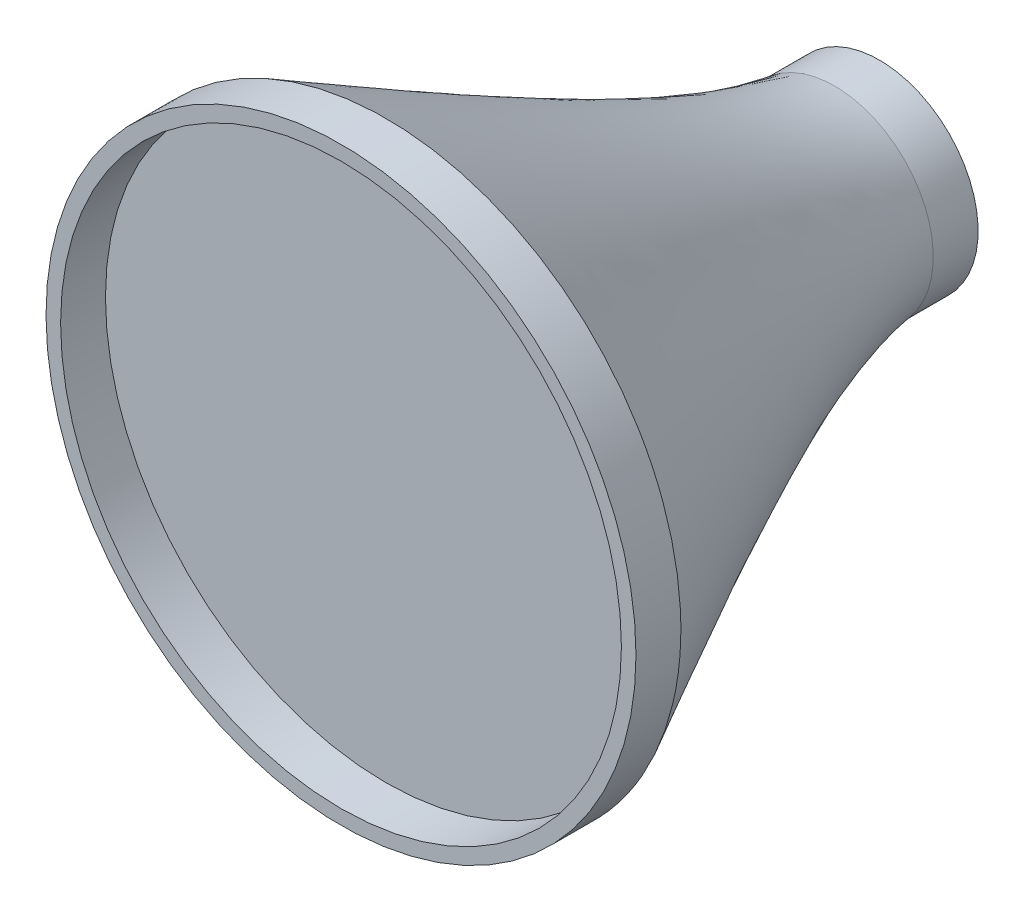
SolidWorks part; units mm, degrees
ref_plane "Front Plane" through (0, 0, 0) normal (0, 0, 1) x (1, 0, 0)
ref_plane "Top Plane" through (0, 0, 0) normal (0, 1, 0) x (1, 0, 0)
ref_plane "Right Plane" through (0, 0, 0) normal (1, 0, 0) x (0, 0, -1)
sketch "Sketch1" plane through (0, 0, 0) normal (0, 0, 1) x (1, 0, 0)
  circle A0 centre (0, 0) radius 16.7005
  circle A1 centre (0, 0) radius 12.7
ref_plane "Plane1" through (0, 0, -25.4) normal (0, 0, 1) x (1, 0, 0)
sketch "Sketch2" plane through (0, 0, -25.4) normal (0, 0, 1) x (1, 0, 0)
  circle A0 centre (0, 0) radius 5.08
  circle A1 centre (0, 0) radius 5.588
sketch "Sketch3" plane through (0, 0, 0) normal (1, 0, 0) x (0, 0, -1)
  line L0 (0, 0) -> (25.4, 0) construction
loft "Loft1" add section "Sketch1" section "Sketch2" connector at (-15.5316, 6.1381, 0) connector at (-1.0953, 5.4796, -25.4)
sketch "Sketch6" plane through (0, 0, 0) normal (0, 0, 1) x (1, 0, 0)
  circle A0 centre (0, 0) radius 16.7005
  circle A1 centre (0, 0) radius 15.875
extrude "Boss-Extrude1" add sketch "Sketch6" along normal blind 2.54
sketch "Sketch7" plane through (0, 0, -25.4) normal (0, 0, -1) x (-1, 0, 0)
  circle A0 centre (0, 0) radius 5.588
  circle A1 centre (0, 0) radius 5.08
extrude "Boss-Extrude2" add sketch "Sketch7" along normal blind 2.54
sketch "Sketch8" plane through (0, 0, 2.54) normal (0, 0, 1) x (1, 0, 0)
  circle A0 centre (0, 0) radius 16.7005
  circle A1 centre (0, 0) radius 15.875
sketch "Sketch9" plane through (0, 0, -27.94) normal (0, 0, -1) x (-1, 0, 0)
  circle A0 centre (0, 0) radius 5.08
